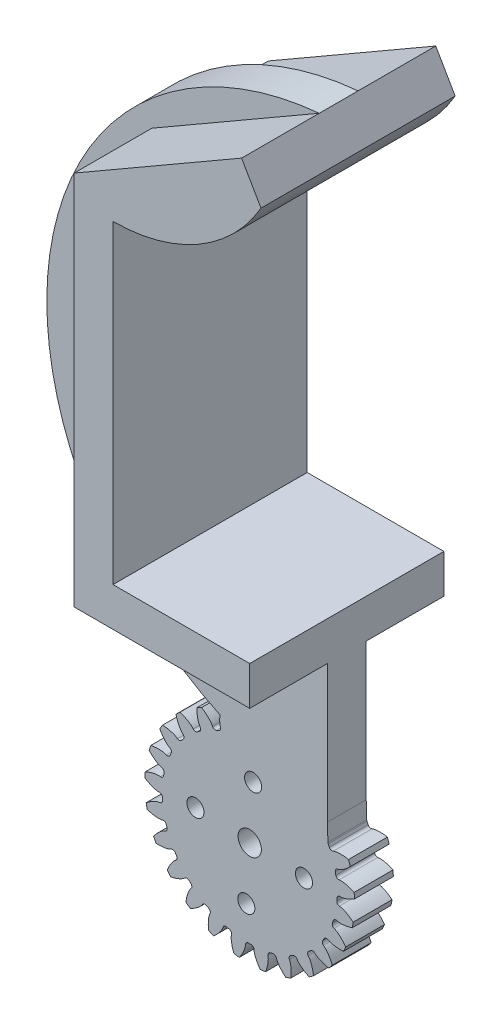
SolidWorks part; units mm, degrees
ref_plane "前视基准面" through (0, 0, 0) normal (0, 0, 1) x (1, 0, 0)
ref_plane "上视基准面" through (0, 0, 0) normal (0, 1, 0) x (1, 0, 0)
ref_plane "右视基准面" through (0, 0, 0) normal (1, 0, 0) x (0, 0, -1)
ref_axis "Axis1" through (0, 0, -88.99) along (0, 0, 1)
sketch "草图1" plane through (0, 0, 0) normal (0, 0, 1) x (1, 0, 0)
  circle A0 centre (0, 0) radius 13.5
extrude "LaShenA" add sketch "草图1" along normal blind 5
sketch "SketchA" plane through (0, 0, 5) normal (0, 0, 1) x (1, 0, 0)
  line L0 (0, 0) -> (-4.9697, 12.552) construction
  arc A0 (-3.9844, 10.5208) -> (-4.2975, 10.3968) centre (0, 0) ccw
  arc A1 (-3.4867, 13.7076) -> (-6.8418, 12.3792) centre (0, 0) ccw
  arc A2 (-4.2975, 10.3968) -> (-4.7863, 10.5857) centre (-4.4427, 10.748) cw
  arc A3 (-3.7574, 10.9931) -> (-3.9844, 10.5208) centre (-4.1189, 10.8762) cw
  circle A4 centre (0, 0) radius 11.7462 construction
  circle A5 centre (0, 0) radius 13.5 construction
  circle A6 centre (0, 0) radius 11.25 construction
  circle A7 centre (0, 0) radius 12.5 construction
  spline S0 degree 3 poles (-3.7574, 10.9931) (-3.7706, 11.0341) (-3.7936, 11.1057) (-3.8159, 11.1929) (-3.8275, 11.2557) (-3.8357, 11.3059) (-3.8435, 11.364) (-3.8507, 11.43) (-3.8569, 11.5041) (-3.8616, 11.586) (-3.8645, 11.6759) (-3.8651, 11.7737) (-3.863, 11.8792) (-3.8578, 11.9925) (-3.8492, 12.1134) (-3.8367, 12.2418) (-3.8199, 12.3776) (-3.7985, 12.5206) (-3.7721, 12.6708) (-3.7402, 12.8279) (-3.7025, 12.9917) (-3.6587, 13.1621) (-3.5901, 13.4028) (-3.5304, 13.5848) (-3.4867, 13.7076) knots 0.117691 0.117691 0.117691 0.117691 0.158672 0.189773 0.203463 0.219643 0.238312 0.25947 0.283117 0.309254 0.337879 0.368994 0.402598 0.438691 0.477273 0.518344 0.561905 0.607955 0.656494 0.707522 0.761039 0.817046 0.875541 1 1 1 1
  spline S1 degree 3 poles (-4.7863, 10.5857) (-4.8047, 10.6247) (-4.8369, 10.6927) (-4.8804, 10.7714) (-4.9149, 10.8252) (-4.9433, 10.8673) (-4.9774, 10.915) (-5.0173, 10.9682) (-5.0635, 11.0264) (-5.1162, 11.0893) (-5.1756, 11.1568) (-5.2421, 11.2285) (-5.3159, 11.304) (-5.3972, 11.383) (-5.4862, 11.4652) (-5.5832, 11.5503) (-5.6884, 11.6378) (-5.802, 11.7274) (-5.924, 11.8188) (-6.0548, 11.9115) (-6.1944, 12.0051) (-6.343, 12.0993) (-6.5577, 12.2278) (-6.7259, 12.3196) (-6.8418, 12.3792) knots 0.117691 0.117691 0.117691 0.117691 0.158672 0.189773 0.203463 0.219643 0.238312 0.25947 0.283117 0.309254 0.337879 0.368994 0.402598 0.438691 0.477273 0.518344 0.561905 0.607955 0.656494 0.707522 0.761039 0.817046 0.875541 1 1 1 1
  dimension "D1" = 0.38
  dimension "Db" = 23.4923
  dimension "Da" = 27
  dimension "Df" = 22.5
  dimension "Dn" = 25
extrude "Cut-ExtrudeA" cut sketch "SketchA" against normal blind 30
pattern_circular "www.KYTool.cn" count 25 over 360 about axis through (0, 0, -88.99) along (0, 0, 1) of "Cut-ExtrudeA"
sketch "草图4" plane through (-1.0086, -38.3291, 5) normal (0, 0, 1) x (1, 0, 0)
  line L0 (1.0086, 38.3291) -> (11.0086, 38.3291) construction
  line L1 (11.0086, 38.3291) -> (11.0086, 68.3291)
  line L2 (6.0086, 46.9893) -> (6.0086, 63.3291)
  line L3 (11.0086, 68.3291) -> (-6.5914, 68.3291)
  line L4 (-6.5914, 68.3291) -> (-6.5914, 108.8291)
  line L5 (-6.5914, 108.8291) -> (12.4612, 119.8291) construction
  line L6 (6.0086, 63.3291) -> (-11.5914, 63.3291)
  line L7 (-11.5914, 63.3291) -> (-11.5914, 111.7158)
  line L8 (-11.5914, 111.7158) -> (9.9612, 124.1592)
  line L9 (9.9612, 124.1592) -> (12.4612, 119.8291)
  line L10 (6.0086, 38.3291) -> (6.0086, 46.9893) construction
  line L11 (6.0086, 38.3291) -> (6.0086, 63.3291) construction
  line L12 (-6.5914, 108.8291) -> (12.9989, 108.8291) construction
  arc A0 (11.0086, 38.3291) -> (6.0086, 46.9893) centre (1.0086, 38.3291) ccw
  arc A1 (6.0086, 46.9893) -> (11.0086, 38.3291) centre (1.0086, 38.3291) ccw construction
  arc A2 (-6.5914, 108.8291) -> (12.4612, 119.8291) centre (-6.5914, 130.8291) ccw
  point P13 (1.0086, 38.3291)
  dimension "D1" = 20
  dimension "D3" = 30
  dimension "D4" = 17.6
  dimension "D5" = 40.5
  dimension "D6" = 22
  dimension "D7" = 120
  dimension "D2" = 5
extrude "凸台-拉伸2" add sketch "草图4" against normal blind 15 and the other way blind 10
sketch "草图6" plane through (-1.0086, -38.3291, 15) normal (0, 0, 1) x (1, 0, 0)
  line L0 (11.0086, 38.3291) -> (11.0086, 68.3291) construction
  line L1 (6.0086, 63.3291) -> (6.0086, 46.9893) construction
  line L2 (11.0086, 38.3291) -> (11.0086, 63.3291)
  line L3 (6.0086, 63.3291) -> (6.0086, 46.9893)
  line L4 (6.0086, 63.3291) -> (11.0086, 63.3291)
  arc A0 (11.0086, 38.3291) -> (6.0086, 46.9893) centre (1.0086, 38.3291) ccw construction
  arc A1 (11.0086, 38.3291) -> (6.0086, 46.9893) centre (1.0086, 38.3291) ccw
extrude "切除-拉伸2" cut sketch "草图6" against normal blind 10 contours L2 L4 L3 A1
sketch "草图8" plane through (-1.0086, -38.3291, 5) normal (0, 0, 1) x (1, 0, 0)
  line L1 (9.9612, 124.1592) -> (-11.5914, 111.7158)
  line L10 (-11.5914, 111.7158) -> (-11.5914, 63.3291)
  line L11 (-11.5914, 63.3291) -> (6.0086, 63.3291)
  line L12 (6.0086, 63.3291) -> (6.0086, 47.813)
  arc A1 (9.9612, 124.1592) -> (6.0086, 47.813) centre (13.5086, 85.7001) ccw
extrude "凸台-拉伸3" add sketch "草图8" against normal blind 5 contours L1 A1 L12 L11 L10 | L1 L10 L11 L12 A1 region at (-13.0456, 42.4923, 5)
sketch "草图10" plane through (-1.0086, -38.3291, -10) normal (0, 0, -1) x (-1, 0, 0)
  line L0 (-6.0086, 63.3291) -> (-6.0086, 46.9893) construction
  line L1 (-11.0086, 38.3291) -> (-11.0086, 68.3291) construction
  line L2 (-6.0086, 63.3291) -> (-6.0086, 46.9893)
  line L3 (-11.0086, 38.3291) -> (-11.0086, 63.3291)
  line L4 (-6.0086, 63.3291) -> (-11.0086, 63.3291)
  arc A0 (-6.0086, 46.9893) -> (-11.0086, 38.3291) centre (-1.0086, 38.3291) ccw construction
  arc A1 (-6.0086, 46.9893) -> (-11.0086, 38.3291) centre (-1.0086, 38.3291) ccw
extrude "切除-拉伸3" cut sketch "草图10" against normal blind 10
sketch "草图12" plane through (-1.0086, -38.3291, 5) normal (0, 0, 1) x (1, 0, 0)
  line L0 (-7.0754, 38.8377) -> (-4.8797, 38.6995) construction
  line L1 (-12.4647, 39.1767) -> (-7.0754, 38.8377) construction
  line L2 (2.5057, 38.2349) -> (6.897, 37.9586) construction
  line L3 (-4.8797, 38.6995) -> (-0.4884, 38.4232) construction
  line L4 (-0.4884, 38.4232) -> (2.5057, 38.2349) construction
  line L5 (9.0926, 37.8205) -> (14.482, 37.4814) construction
  line L6 (6.897, 37.9586) -> (9.0926, 37.8205) construction
  circle A3 centre (1.0086, 38.3291) radius 1.5
  circle A6 centre (-5.9776, 38.7686) radius 1.1
  circle A7 centre (1.4482, 45.3152) radius 1.1
  circle A8 centre (7.9948, 37.8895) radius 1.1
  circle A9 centre (0.5691, 31.3429) radius 1.1
  point P5 (1.0086, 38.3291)
  point P7 (1.0086, 38.3291)
  point P20 (0, 0)
  point P21 (1.0086, 38.3291)
  dimension "D1" = 2.2
  dimension "D2" = 7
  dimension "D5" = 3
  dimension "D3" = 4
extrude "切除-拉伸4" cut sketch "草图12" against normal through all
sketch "草图13" plane through (0, 0, 5) normal (0, 0, 1) x (1, 0, 0)
  arc A0 (-1.2428, 11.1811) -> (-1.1047, 11.2242) centre (-1.2847, 11.5588) ccw construction
  arc A1 (-1.2428, 11.1811) -> (-1.5769, 11.1389) centre (0, 0) ccw construction
  arc A2 (-2.0034, 11.4435) -> (-1.5769, 11.1389) centre (-1.6302, 11.5152) ccw construction
  arc A3 (-2.0335, 11.5875) -> (-1.1047, 11.2242) centre (12.5, 47.3711) ccw construction
  arc A4 (-1.2428, 11.1811) -> (-1.1047, 11.2242) centre (-1.2847, 11.5588) ccw
  arc A5 (-1.2428, 11.1811) -> (-1.5769, 11.1389) centre (0, 0) ccw
  arc A6 (-2.0034, 11.4435) -> (-1.5769, 11.1389) centre (-1.6302, 11.5152) ccw
  arc A7 (-2.0335, 11.5875) -> (-1.1047, 11.2242) centre (12.5, 47.3711) ccw
  spline S0 degree 3 poles (-1740.1357, -977.653) (-21.788, 18.0971) (16.1078, 14.0998) (-18.4486, -0.4871) (1992.5488, -134.2961) knots -3.507933 -3.507933 -3.507933 -3.507933 0.959019 5.540456 5.540456 5.540456 5.540456 only from (-2.0335, 11.5875) to (-2.0034, 11.4435) construction
  spline S1 degree 3 poles (-2.0335, 11.5875) (-2.0321, 11.5815) (-2.0208, 11.5338) (-2.0115, 11.4858) (-2.0034, 11.4435) knots 0.953132 0.953132 0.953132 0.953132 0.959019 1 1 1 1
extrude "凸台-拉伸4" add sketch "草图13" against normal blind 5
sketch "草图14" plane through (0, 0, 5) normal (0, 0, 1) x (1, 0, 0)
  line L0 (10, 7.3128) -> (10.068, 5.0971)
  arc A0 (10.2643, 5.4415) -> (10.1065, 4.9419) centre (10.4478, 5.1088) ccw construction
  arc A1 (11.5869, 6.9277) -> (11.2019, 7.5345) centre (0, 0) ccw construction
  arc A2 (10.2643, 5.4415) -> (10.068, 5.0971) centre (10.4478, 5.1088) ccw
  arc A3 (11.5869, 6.9277) -> (11.2019, 7.5345) centre (0, 0) ccw
  arc A4 (10.068, 5.0971) -> (10.1065, 4.9419) centre (10.4478, 5.1088) ccw construction
  spline S0 degree 3 poles (942.0057, -1763.3934) (-63.6825, 103.3117) (23.0569, 25.4687) (11.4235, 6.6545) (11.34, 6.5269) (11.2576, 6.4079) (11.1769, 6.2975) (11.0981, 6.1953) (11.0216, 6.1013) (10.9479, 6.0152) (10.8771, 5.9368) (10.8098, 5.8659) (10.7462, 5.8024) (10.6867, 5.7459) (10.6315, 5.6961) (10.581, 5.6529) (10.5355, 5.6159) (10.4952, 5.5849) (10.4437, 5.5471) (6.3514, 2.9396) (-6.1634, 17.3943) (487.9667, -1936.3621) knots -20.61536 -20.61536 -20.61536 -20.61536 0.41017 0.461198 0.509737 0.555786 0.599347 0.640418 0.679001 0.715094 0.748698 0.779812 0.808438 0.834574 0.858221 0.879379 0.898048 0.914228 0.927918 0.959019 5.540328 5.540328 5.540328 5.540328 only from (11.5869, 6.9277) to (10.2643, 5.4415) construction
  spline S1 degree 3 poles (1119.4986, -1656.3495) (3.8665, -54.038) (-1.6438, 3.7827) (10.1041, 7.3448) (10.2134, 7.3749) (10.331, 7.404) (10.457, 7.4318) (10.5913, 7.4579) (10.734, 7.4817) (10.885, 7.5029) (32.8618, 10.0185) (66.364, -101.608) (-1194.451, 1603.1302) knots -11.285002 -11.285002 -11.285002 -11.285002 0.368994 0.402598 0.438691 0.477273 0.518344 0.561905 0.607955 0.656494 0.707522 21.732893 21.732893 21.732893 21.732893 only from (10, 7.3128) to (11.2019, 7.5345) construction
  spline S2 degree 3 poles (11.5869, 6.9277) (11.5341, 6.8347) (11.4528, 6.6993) (11.34, 6.5269) (11.2576, 6.4079) (11.1769, 6.2975) (11.0981, 6.1953) (11.0216, 6.1013) (10.9479, 6.0152) (10.8771, 5.9368) (10.8098, 5.8659) (10.7462, 5.8024) (10.6867, 5.7459) (10.6315, 5.6961) (10.581, 5.6529) (10.5355, 5.6159) (10.4952, 5.5849) (10.4437, 5.5471) (10.3678, 5.4988) (10.302, 5.4623) (10.2643, 5.4415) knots 0.358993 0.358993 0.358993 0.358993 0.461198 0.509737 0.555786 0.599347 0.640418 0.679001 0.715094 0.748698 0.779812 0.808438 0.834574 0.858221 0.879379 0.898048 0.914228 0.927918 0.959019 1 1 1 1
  spline S3 degree 3 poles (10, 7.3128) (10.0338, 7.3235) (10.1038, 7.3447) (10.2134, 7.3749) (10.331, 7.404) (10.457, 7.4318) (10.5913, 7.4579) (10.734, 7.4817) (10.9381, 7.5104) (11.0952, 7.5263) (11.2019, 7.5345) knots 0.368766 0.368766 0.368766 0.368766 0.402598 0.438691 0.477273 0.518344 0.561905 0.607955 0.656494 0.758699 0.758699 0.758699 0.758699
extrude "切除-拉伸5" cut sketch "草图14" against normal blind 10
